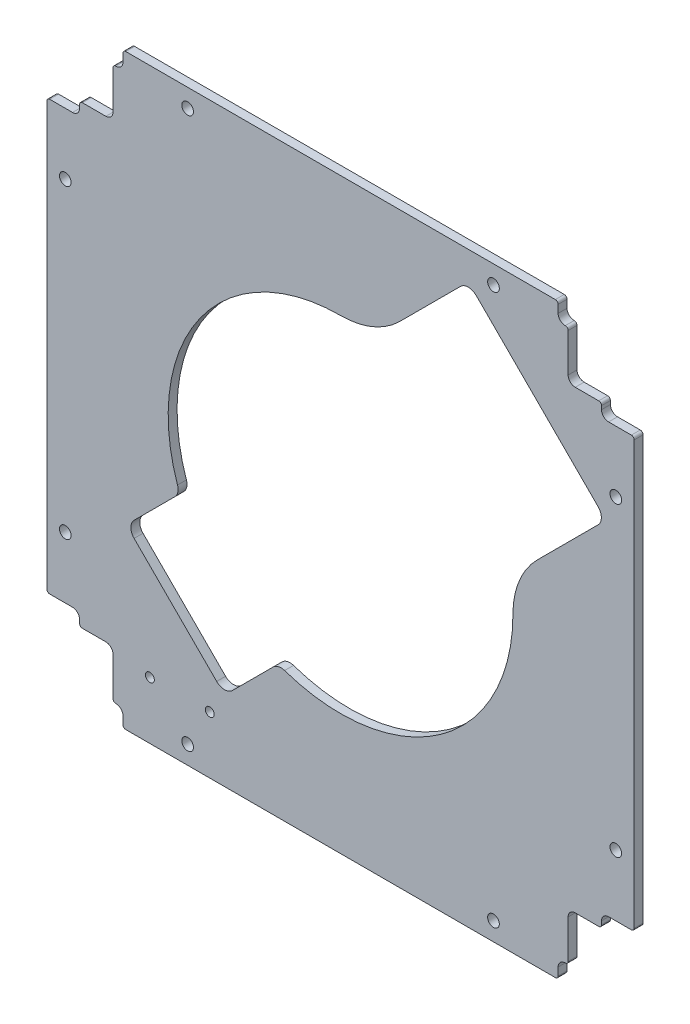
SolidWorks part; units mm, degrees
material "FR4_stuffedProtoboard"
ref_plane "Front Plane" through (0, 0, 0) normal (0, 0, 1) x (1, 0, 0)
ref_plane "Top Plane" through (0, 0, 0) normal (0, 1, 0) x (1, 0, 0)
ref_plane "Right Plane" through (0, 0, 0) normal (1, 0, 0) x (0, 0, -1)
sketch "Sketch1" plane through (0, 0, 0) normal (0, 0, 1) x (1, 0, 0)
  line L0 (53, 53) -> (-53, -53) construction
  line L1 (53, 53) -> (-53, 53)
  line L2 (53, 53) -> (53, -53)
  line L3 (53, -53) -> (-53, -53)
  line L4 (-53, 53) -> (-53, -53)
  point P4 (0, 0)
  dimension "D1" = 106
  dimension "D2" = 106
extrude "mainOutline" add sketch "Sketch1" along normal blind 1.6
sketch "axisLabels" plane through (0, 0, 0) normal (0, 0, -1) x (-1, 0, 0)
  text T0 "+Y"
  text T1 "+X"
sketch "Sketch4" plane through (0, 0, 0) normal (0, 0, -1) x (-1, 0, 0)
  line L10 (-53, 53) -> (53, 53) construction
  line L29 (41.3, 53) -> (41.3, 41.3)
  line L31 (53, 41.3) -> (41.3, 41.3)
  line L46 (53, 53) -> (53, -53) construction
  line L51 (53, 41.3) -> (53, 53)
  line L52 (53, 53) -> (41.3, 53)
  dimension "D11" = 11.7
  dimension "D12" = 11.7
extrude "railCutouts" cut sketch "Sketch4" against normal through all
sketch "Sketch13" plane through (0, 0, 0) normal (0, 0, -1) x (-1, 0, 0)
  line L0 (47.3, 38.9) -> (47.3, 41.3)
  line L2 (53, 41.3) -> (53, 38.9)
  line L5 (41.3, 53) -> (39.5, 53)
  line L6 (41.3, 53) -> (41.3, 50)
  line L7 (41.3, 50) -> (39.5, 50)
  line L8 (39.5, 53) -> (39.5, 50)
  line L9 (53, 41.3) -> (53, -53) construction
  line L10 (53, 41.3) -> (47.3, 41.3)
  line L12 (53, 38.9) -> (47.3, 38.9)
  line L13 (41.3, 41.3) -> (53, 41.3) construction
  dimension "D1" = 5.7
  dimension "D3" = 2.4
  dimension "D5" = 1.8
  dimension "D6" = 3
extrude "filletCutouts" cut sketch "Sketch13" against normal through all both and the other way through all
sketch "Sketch5" plane through (0, 0, 0) normal (0, 0, -1) x (-1, 0, 0)
  line L23 (42.198, 42.198) -> (45.4803, 45.4803) construction
  line L24 (41.3, 43.0961) -> (44.5823, 46.3784)
  line L25 (43.0961, 41.3) -> (46.3784, 44.5823)
  line L41 (41.3, 50) -> (41.3, 41.3) construction
  arc A14 (41.3, 43.0961) -> (43.0961, 41.3) centre (42.198, 42.198) ccw
  arc A15 (46.3784, 44.5823) -> (44.5823, 46.3784) centre (45.4803, 45.4803) ccw
  point P0 (41.3, 41.3)
  point P52 (43.8392, 43.8392)
  dimension "D14" = 1.27
  dimension "D7" = 45
extrude "dogbone" [suppressed] cut sketch "Sketch5" against normal through all
sketch "Sketch14" plane through (0, 0, 1.6) normal (0, 0, 1) x (1, 0, 0)
  point P1 (-47.3, 38.9)
sketch "Sketch27" plane through (0, 0, 1.6) normal (0, 0, 1) x (1, 0, 0)
  line L0 (-40.928, 42.198) -> (-40.928, 49.628)
  line L1 (-48.198, 38.528) -> (-53, 38.528)
  line L2 (-53, 38.9) -> (-53, -53) construction
  line L3 (-53, 38.528) -> (-53, 53)
  line L4 (-53, 53) -> (-39.128, 53)
  line L5 (-39.128, 53) -> (-39.128, 50.898)
  line L6 (-40.928, 49.628) -> (-40.398, 49.628)
  line L7 (-42.198, 40.928) -> (-46.928, 40.928)
  line L8 (-46.928, 40.928) -> (-46.928, 39.798)
  line L10 (53, 53) -> (-39.5, 53) construction
  arc A0 (-42.198, 40.928) -> (-40.928, 42.198) centre (-42.198, 42.198) ccw
  arc A1 (-40.398, 49.628) -> (-39.128, 50.898) centre (-40.398, 50.898) ccw
  arc A2 (-48.198, 38.528) -> (-46.928, 39.798) centre (-48.198, 39.798) ccw
  dimension "D1" = 1.27
extrude "smoothCorner" cut sketch "Sketch27" against normal blind 10
pattern_sketch "Sketch-Pattern1" [suppressed] of bodies 103 driven by "Sketch14"
mirror "Mirror1" about plane through (0, 0, 0) normal (1, 0, 0) of "smoothCorner", "filletCutouts", "railCutouts"
mirror "Mirror2" about plane through (0, 0, 0) normal (0, 1, 0) of "Mirror1"
fillet "Fillet1" [suppressed] radius 0.5
fillet "Fillet10" radius 0.5 8 edges at (46.928, -40.928, 0.8) (40.928, -49.628, 0.8) (40.928, 49.628, 0.8) (46.928, 40.928, 0.8) (-46.928, 40.928, 0.8) (-40.928, 49.628, 0.8) (-46.928, -40.928, 0.8) (-40.928, -49.628, 0.8)
hole_wizard "M2 Clearance Hole1" positions "Sketch8" profile "Sketch9" hole size "M2" standard "ANSI Metric" end condition through all
sketch "Sketch8" plane through (0, 0, 0) normal (0, 0, -1) x (-1, 0, 0)
  line L0 (53, 38.528) -> (53, -38.528) construction
  line L1 (39.128, -53) -> (-39.128, -53) construction
  line L2 (-53, -38.528) -> (-53, 38.528) construction
  line L3 (53, 0) -> (-53, 0) construction
  line L5 (0, -53) -> (0, -11.6379) construction
  line L6 (53, 38.528) -> (53, -38.528) construction
  point P0 (49.5, -27.5)
  point P1 (27.5, -49.5)
  point P5 (-49.5, -27.5)
  point P30 (-27.5, -49.5)
  point P31 (-27.5, 49.5)
  point P32 (-49.5, 27.5)
  point P33 (27.5, 49.5)
  point P34 (49.5, 27.5)
  dimension "D1" = 3.5
  dimension "D2" = 3.5
  dimension "D3" = 55
  dimension "D4" = 3.5
  dimension "D5" = 55
  dimension "D6" = 55
sketch "Sketch9" plane through (-49.5, -27.5, 0) normal (1, 0, 0) x (0, 1, 0)
  line L0 (0, 0) -> (0, 1.6)
  line L1 (0, 1.6) -> (1.05, 1.6)
  line L2 (1.05, 1.6) -> (1.05, 0)
  line L5 (1.05, 0) -> (0, 0)
  line L11 (0, -6.35) -> (0, 107.95) construction
  dimension "Thru Hole Dia." = 2.1
  dimension "Thru Hole Depth" = 1.6
sketch "Sketch15" plane through (0, 0, 0) normal (0, 0, -1) x (-1, 0, 0)
  line L0 (-39.128, 53) -> (39.128, 53) construction
  line L1 (45, 53) -> (-45, 53)
  line L2 (45, 53) -> (45, 47.8)
  line L3 (45, 47.8) -> (-45, 47.8)
  line L4 (-45, 53) -> (-45, 47.8)
  line L5 (45, -53) -> (-45, -53)
  line L6 (45, -53) -> (45, -47.8)
  line L7 (45, -47.8) -> (-45, -47.8)
  line L8 (-45, -53) -> (-45, -47.8)
  line L9 (39.128, -53) -> (-39.128, -53) construction
  line L10 (-53, -38.528) -> (-53, 38.528) construction
  line L11 (-53, 45) -> (-47.8, 45)
  line L12 (-53, 45) -> (-53, -45)
  line L13 (-53, -45) -> (-47.8, -45)
  line L14 (-47.8, 45) -> (-47.8, -45)
  line L15 (53, 45) -> (47.8, 45)
  line L16 (53, 45) -> (53, -45)
  line L17 (53, -45) -> (47.8, -45)
  line L18 (47.8, 45) -> (47.8, -45)
  line L19 (53, 38.528) -> (53, -38.528) construction
  point P8 (0, 53)
  point P11 (0, -53)
  point P22 (-53, 0)
  point P25 (53, 0)
  dimension "D1" = 90
  dimension "D3" = 5.2
  dimension "D5" = 5.2
extrude "Cut-Extrude5" cut sketch "Sketch15" against normal blind 0.001
sketch "Sketch11" plane through (0, 0, 0) normal (0, 0, -1) x (-1, 0, 0)
  circle A0 centre (0, 0) radius 31
  dimension "D1" = 62
extrude "Cut-Extrude2" cut sketch "Sketch11" against normal through all both and the other way through all
sketch "Sketch28" plane through (0, 0, 0) normal (0, 0, -1) x (-1, 0, 0)
  line L0 (12.3744, 12.3744) -> (-22.981, 47.7297)
  line L1 (12.3744, 12.3744) -> (-12.3744, -12.3744)
  line L2 (-22.981, 47.7297) -> (-47.7297, 22.981)
  line L3 (-12.3744, -12.3744) -> (-47.7297, 22.981)
  line L4 (-47.8, -38.592) -> (-47.8, 38.592) construction
  line L5 (8.8388, 8.8388) -> (-8.8388, -8.8388)
  line L6 (8.8388, 8.8388) -> (38.5373, -20.8597)
  line L7 (-8.8388, -8.8388) -> (20.8597, -38.5373)
  line L8 (38.5373, -20.8597) -> (20.8597, -38.5373)
  circle M5 centre (0, 0) radius 31
  dimension "D1" = 35
  dimension "D2" = 50
  dimension "D3" = 45
  dimension "D4" = 25
  dimension "D5" = 42
extrude "Cut-Extrude7" cut sketch "Sketch28" against normal blind 10 contours L1 L7 L6 M5 | L3 L1 L0 M5 | L8 L6 L7 M5 | L3 L0 L2 M5 region at (10.377, 10.377, 0) region at (27.981, 27.981, 0) region at (-10.6626, -10.6626, 0) region at (-25.4866, -25.4866, 0)
fillet "Fillet11" radius 2 6 edges at (47.7297, 22.981, 0.8) (22.981, 47.7297, 0.8) (-20.8597, -38.5373, 0.8) (-38.5373, -20.8597, 0.8) (-11.2205, -28.8981, 0.8) (-28.8981, -11.2205, 0.8)
fillet "Fillet13" radius 15 2 edges at (30.4679, 5.7191, 0.8) (5.7191, 30.4679, 0.8)
sketch "Sketch16" [suppressed] plane through (0, 0, 1.6) normal (0, 0, 1) x (1, 0, 0)
  line L0 (-39.128, -53) -> (39.128, -53) construction
  line L1 (39.128, 53) -> (-39.128, 53) construction
  line L8 (-45, -53) -> (45, -53)
  line L9 (45, -53) -> (45, -47.8)
  line L10 (45, -47.8) -> (-45, -47.8)
  line L11 (-45, -47.8) -> (-45, -53)
  line L16 (45, 53) -> (-45, 53)
  line L17 (45, 47.8) -> (45, 53)
  line L18 (-45, 47.8) -> (45, 47.8)
  line L19 (-45, 53) -> (-45, 47.8)
  line L20 (-47.8, 45) -> (-53, 45)
  line L21 (-53, 45) -> (-53, -45)
  line L22 (-53, -45) -> (-47.8, -45)
  line L23 (-47.8, -45) -> (-47.8, 45)
  line L24 (-47.8, 45) -> (-53, 45)
  line L25 (-53, 45) -> (-53, -45)
  line L26 (-53, -45) -> (-47.8, -45)
  line L27 (-47.8, -45) -> (-47.8, 45)
  line L28 (53, 45) -> (47.8, 45)
  line L29 (47.8, 45) -> (47.8, -45)
  line L30 (47.8, -45) -> (53, -45)
  line L31 (53, -45) -> (53, 45)
  line L32 (53, 45) -> (47.8, 45)
  line L33 (47.8, 45) -> (47.8, -45)
  line L34 (47.8, -45) -> (53, -45)
  line L35 (53, -45) -> (53, 45)
  dimension "D1" = 5.2
  dimension "D3" = 0
  dimension "D4" = 0
extrude "Cut-Extrude6" [suppressed] cut sketch "Sketch16" against normal blind 0.001
sketch "Sketch30" [suppressed] plane through (0, 0, 0) normal (0, 0, -1) x (-1, 0, 0)
  line L0 (-18.93, -39.33) -> (-2.75, -23.15)
  line L1 (-2.75, -23.15) -> (2.75, -23.15)
  line L2 (2.75, -23.15) -> (18.93, -39.33)
  line L3 (-39.33, -18.93) -> (-23.15, -2.75)
  line L4 (-23.15, -2.75) -> (-23.15, 2.75)
  line L5 (-23.15, 2.75) -> (-39.33, 18.93)
  line L6 (-18.93, 39.33) -> (-2.75, 23.15)
  line L7 (-2.75, 23.15) -> (2.75, 23.15)
  line L8 (2.75, 23.15) -> (18.93, 39.33)
  line L9 (39.33, -18.93) -> (23.15, -2.75)
  line L10 (23.15, -2.75) -> (23.15, 2.75)
  line L11 (23.15, 2.75) -> (39.33, 18.93)
  line L12 (0, -23.15) -> (0, 23.15) construction
  line L13 (-23.15, 0) -> (23.15, 0) construction
  arc A0 (-18.93, -39.33) -> (-39.33, -18.93) centre (-17.5661, -17.5661) cw
  arc A1 (-39.33, 18.93) -> (-18.93, 39.33) centre (-17.5661, 17.5661) cw
  arc A2 (18.93, 39.33) -> (39.33, 18.93) centre (17.5661, 17.5661) cw
  arc A3 (39.33, -18.93) -> (18.93, -39.33) centre (17.5661, -17.5661) cw
  dimension "D5" = 21.8066
  dimension "D1" = 135
  dimension "D2" = 28.85
  dimension "D3" = 22.882
  dimension "D4" = 5.5
extrude "Cut-Extrude8" [suppressed] cut sketch "Sketch30" against normal blind 10
sketch "Sketch29" plane through (0, 0, 0) normal (0, 0, -1) x (-1, 0, 0)
  circle A0 centre (34.285, -42.5) radius 0.8
  circle A1 centre (23.515, -42.5) radius 0.8
  circle A2 centre (49.5, -27.5) radius 1.05 construction
  circle A4 centre (27.5, -49.5) radius 1.05 construction
  dimension "D1" = 1.6
  dimension "D2" = 10.77
  dimension "D3" = 7
  dimension "D4" = 25.985
extrude "Connector Location" cut sketch "Sketch29" against normal blind 10
sketch "Sketch31" plane through (0, 0, 0) normal (0, 0, -1) x (-1, 0, 0)
  line L1 (52.8, -52.8) -> (-52.8, -52.8)
  line L2 (52.8, -52.8) -> (52.8, 52.8)
  line L3 (52.8, 52.8) -> (-52.8, 52.8)
  line L4 (-52.8, -52.8) -> (-52.8, 52.8)
  circle A0 centre (27.5, -49.5) radius 1.05 construction
  circle A1 centre (49.5, -27.5) radius 1.05 construction
  circle A2 centre (-27.5, 49.5) radius 1.05 construction
  circle A5 centre (-49.5, 27.5) radius 1.05 construction
  dimension "D2" = 3.3
  dimension "D4" = 3.3
  dimension "D1" = 3.3
  dimension "D3" = 3.3
extrude "Cut-Extrude-Thin1" cut sketch "Sketch31" against normal through all both and the other way through all thin thin type one direction wall 10
fillet "Fillet12" radius 0.5 8 edges at (-52.8, 38.528, 0.8005) (-39.128, 52.8, 0.8005) (39.128, 52.8, 0.8005) (52.8, 38.528, 0.8005) (52.8, -38.528, 0.8005) (39.128, -52.8, 0.8005) (-39.128, -52.8, 0.8005) (-52.8, -38.528, 0.8005)
equation "\"ConnectorSideDistance\"= 25.985"
equation "\"ConnectorTopDistance\"= 7.0"
equation "\"D3@Sketch29\"=\"ConnectorTopDistance\""
equation "\"D4@Sketch29\"=\"ConnectorSideDistance\""
